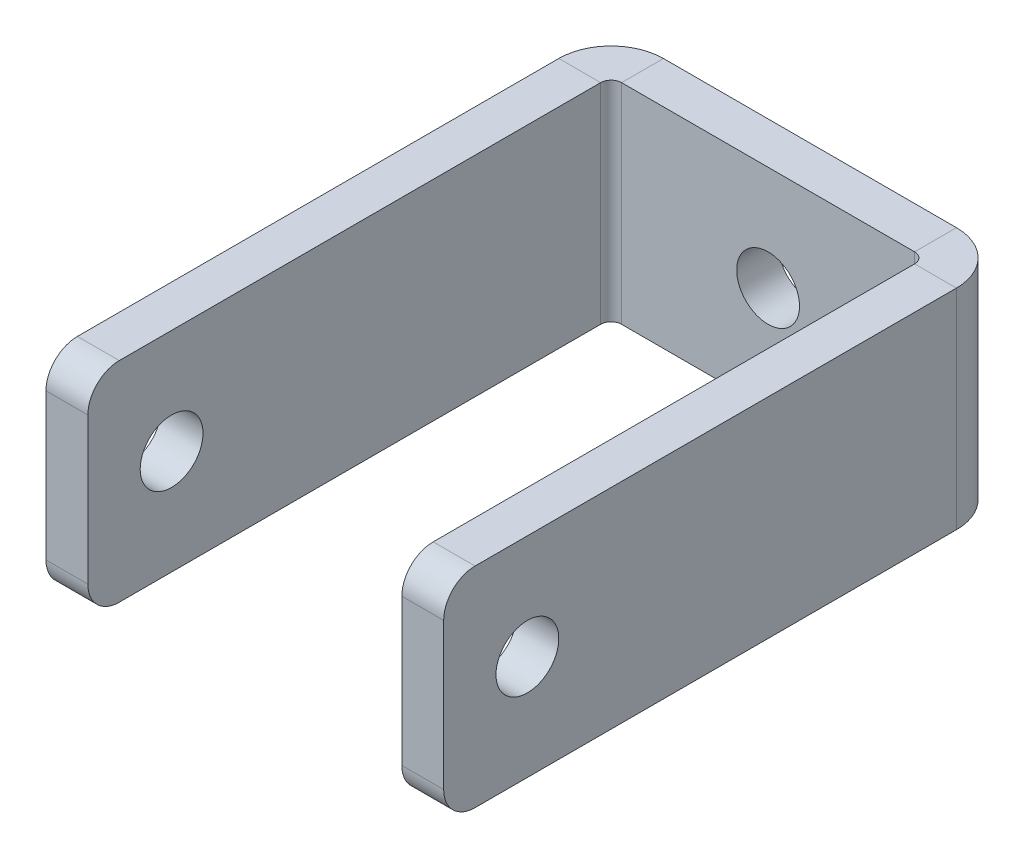
SolidWorks part; units mm, degrees
note: The reader was unsure of these and kept them because the rebuilt part matched: flange length of "边线-法兰1".
ref_plane "前视基准面" through (0, 0, 0) normal (0, 0, 1) x (1, 0, 0)
ref_plane "上视基准面" through (0, 0, 0) normal (0, 1, 0) x (1, 0, 0)
ref_plane "右视基准面" through (0, 0, 0) normal (1, 0, 0) x (0, 0, -1)
sketch "草图1" plane through (0, 0, 0) normal (0, 0, 1) x (1, 0, 0)
  line L1 (15, -10) -> (-15, -10)
  line L2 (15, -10) -> (15, 10)
  line L3 (15, 10) -> (-15, 10)
  line L4 (-15, -10) -> (-15, 10)
  line L5 (15, -10) -> (-15, 10) construction
  line L6 (15, 10) -> (-15, -10) construction
  point P0 (0, 0)
  dimension "D1" = 30
  dimension "D2" = 20
base flange "基体-法兰1" sketch "草图1" thickness 4 reverse thickness direction no parameters "D1"=10
edge flange "边线-法兰1" sketch "草图10" flange profiles "草图10", "草图11" flange angle 90 flange length 50 flange position material outside bend radius 1 thickness 4 relief rectangular parameters "D6"=10, "D8"=1
sketch "草图10" plane through (-15, 0, 0) normal (-1, 0, 0) x (0, -1, 0)
  line L2 (-10, 0) -> (-10, 50)
  line L3 (-10, 50) -> (10, 50)
  line L4 (10, 50) -> (10, 0)
  line L7 (-10, 0) -> (10, 0) construction
  line L8 (-10, 0) -> (10, 0)
sketch "草图11" plane through (15, 0, 0) normal (1, 0, 0) x (0, 1, 0)
  line L0 (-10, 0) -> (10, 0) construction
  line L1 (-10, 0) -> (10, 0)
  line L2 (-10, 0) -> (-10, 50)
  line L3 (-10, 50) -> (10, 50)
  line L4 (10, 50) -> (10, 0)
bend "边线折弯1" bend radius 1 bend angle 90 parameters "D5"=1
bend "边线折弯2" bend radius 1 bend angle 90 parameters "D5"=2
fillet "圆角1" radius 3 4 edges at (17, 10, 50) (17, -10, 50) (-17, 10, 50) (-17, -10, 50)
sketch "草图12" plane through (0, 0, 0) normal (0, 0, 1) x (1, 0, 0)
  circle A0 centre (0, 0) radius 3
  dimension "D1" = 6
extrude "切除-拉伸1" cut sketch "草图12" against normal blind 10 normal cut yes
sketch "草图13" plane through (-19, 0, 0) normal (-1, 0, 0) x (0, 0, 1)
  line L0 (50, -7) -> (50, 7) construction
  circle A0 centre (42, 0) radius 3
  dimension "D1" = 6
  dimension "D2" = 8
extrude "切除-拉伸2" cut sketch "草图13" against normal through all normal cut yes
sketch "折弯-线1" [suppressed] plane through (0, 0, 0) normal (0, 1, 0) x (1, 0, 0)
sketch "边界框1" [suppressed] plane through (0, 0, 0) normal (0, 1, 0) x (1, 0, 0)
sheet metal parameters "钣金1" thickness 4 parameters "D1"=10
flat pattern "平板型式1" [suppressed]
sketch "折弯-线2" plane through (0, 0, 0) normal (0, 1, 0) x (1, 0, 0)
sketch3d "边界框2" [suppressed]
  line L0 (15, -10, 0) -> (-15, -10, 0) construction
  line L1 (15, 10, 0) -> (-15, 10, 0) construction
  line L2 (15, -10, 0) -> (15, 10, 0) construction
  line L3 (-15, -10, 0) -> (-15, 10, 0) construction
sheet metal parameters "钣金2" thickness 4 parameters "D1"=10
flat pattern "平板型式1"
sketch "折弯-线2" plane through (0, 0, 0) normal (0, 0, 1) x (1, 0, 0)
  line L0 (16.3562, -10) -> (16.3562, 10) construction
  line L1 (-16.3562, 10) -> (-16.3562, -10) construction
  line L2 (16.3562, -10) -> (16.3562, 10) construction
  line L3 (-16.3562, 10) -> (-16.3562, -10) construction
sketch3d "边界框2" [suppressed]
  line L0 (-47.7124, 10, 0) -> (47.7124, 10, 0) construction
  line L1 (-47.7124, -10, 0) -> (47.7124, -10, 0) construction
  line L2 (-47.7124, 10, 0) -> (-47.7124, -10, 0) construction
  line L3 (47.7124, 10, 0) -> (47.7124, -10, 0) construction
bend of the flat pattern "展开-<边线折弯1>1"
bend of the flat pattern "展开-<边线折弯2>1"
sheet metal parameters "钣金3" thickness 4 parameters "D1"=10
flat pattern "平板型式1"
sketch "折弯-线2" plane through (0, 0, 0) normal (0, 0, 1) x (1, 0, 0)
  line L0 (16.3562, -10) -> (16.3562, 10) construction
  line L1 (-16.3562, 10) -> (-16.3562, -10) construction
  line L2 (16.3562, -10) -> (16.3562, 10) construction
  line L3 (-16.3562, 10) -> (-16.3562, -10) construction
sketch3d "边界框2" [suppressed]
  line L0 (-47.7124, 10, 0) -> (47.7124, 10, 0) construction
  line L1 (-47.7124, -10, 0) -> (47.7124, -10, 0) construction
  line L2 (-47.7124, 10, 0) -> (-47.7124, -10, 0) construction
  line L3 (47.7124, 10, 0) -> (47.7124, -10, 0) construction
bend of the flat pattern "展开-<边线折弯1>1"
bend of the flat pattern "展开-<边线折弯2>1"
sheet metal parameters "钣金4" thickness 4 parameters "D1"=10
flat pattern "平板型式1"
sketch "折弯-线2" plane through (0, 0, 0) normal (0, 0, 1) x (1, 0, 0)
  line L0 (16.3562, -10) -> (16.3562, 10) construction
  line L1 (-16.3562, 10) -> (-16.3562, -10) construction
  line L2 (16.3562, -10) -> (16.3562, 10) construction
  line L3 (-16.3562, 10) -> (-16.3562, -10) construction
sketch3d "边界框2" [suppressed]
  line L0 (-67.7124, 10, 0) -> (67.7124, 10, 0) construction
  line L1 (-67.7124, -10, 0) -> (67.7124, -10, 0) construction
  line L2 (-67.7124, 10, 0) -> (-67.7124, -10, 0) construction
  line L3 (67.7124, 10, 0) -> (67.7124, -10, 0) construction
bend of the flat pattern "展开-<边线折弯1>1"
bend of the flat pattern "展开-<边线折弯2>1"
